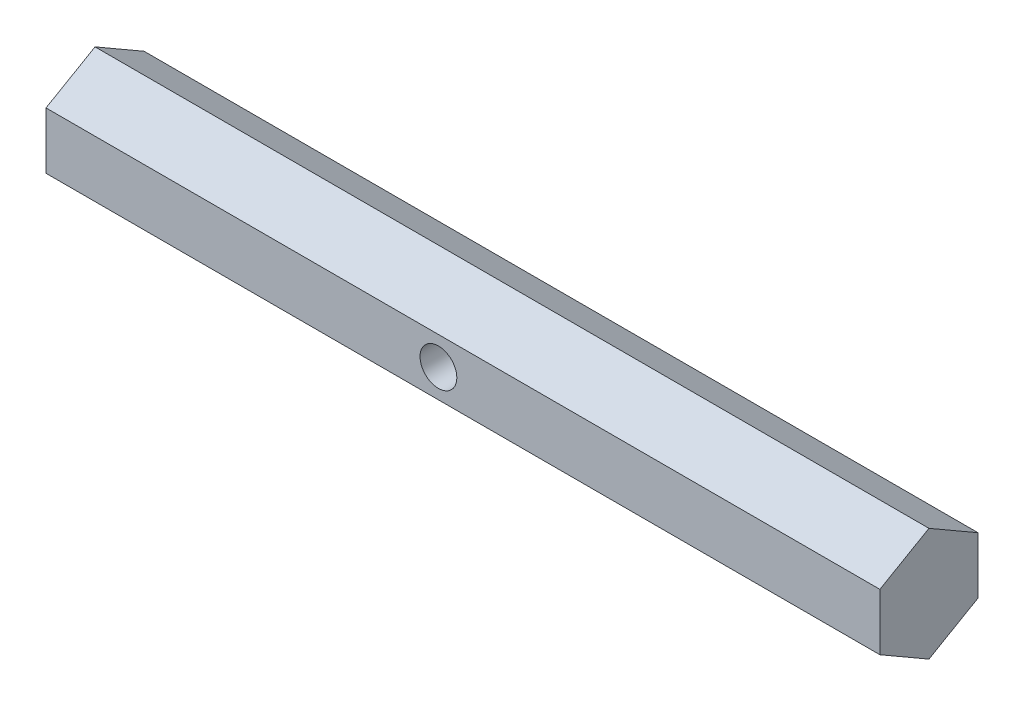
SolidWorks part; units mm, degrees
ref_plane "Front" through (0, 0, 0) normal (0, 0, 1) x (1, 0, 0)
ref_plane "Top" through (0, 0, 0) normal (0, 1, 0) x (1, 0, 0)
ref_plane "Right" through (0, 0, 0) normal (1, 0, 0) x (0, 0, -1)
sketch "Sketch1" plane through (0, 0, 0) normal (1, 0, 0) x (0, 0, -1)
  line L1 (6.35, -3.6662) -> (6.35, 3.6662)
  line L2 (6.35, 3.6662) -> (0, 7.3323)
  line L3 (0, 7.3323) -> (-6.35, 3.6662)
  line L4 (-6.35, 3.6662) -> (-6.35, -3.6662)
  line L5 (-6.35, -3.6662) -> (0, -7.3323)
  line L6 (0, -7.3323) -> (6.35, -3.6662)
  circle A0 centre (0, 0) radius 6.35 construction
  dimension "D1" = 12.7
extrude "Boss-Extrude1" add sketch "Sketch1" along normal blind 107.95
sketch "Sketch2" plane through (0, 0, 6.35) normal (0, 0, 1) x (1, 0, 0)
  line L0 (0, 3.6662) -> (0, -3.6662) construction
  circle A0 centre (50.8, 0) radius 2.3812
  point P2 (0, 0)
  point P3 (0, 0)
  point P4 (0, 0)
  dimension "D2" = 4.7625
  dimension "D1" = 50.8
extrude "Cut-Extrude1" cut sketch "Sketch2" against normal through all
